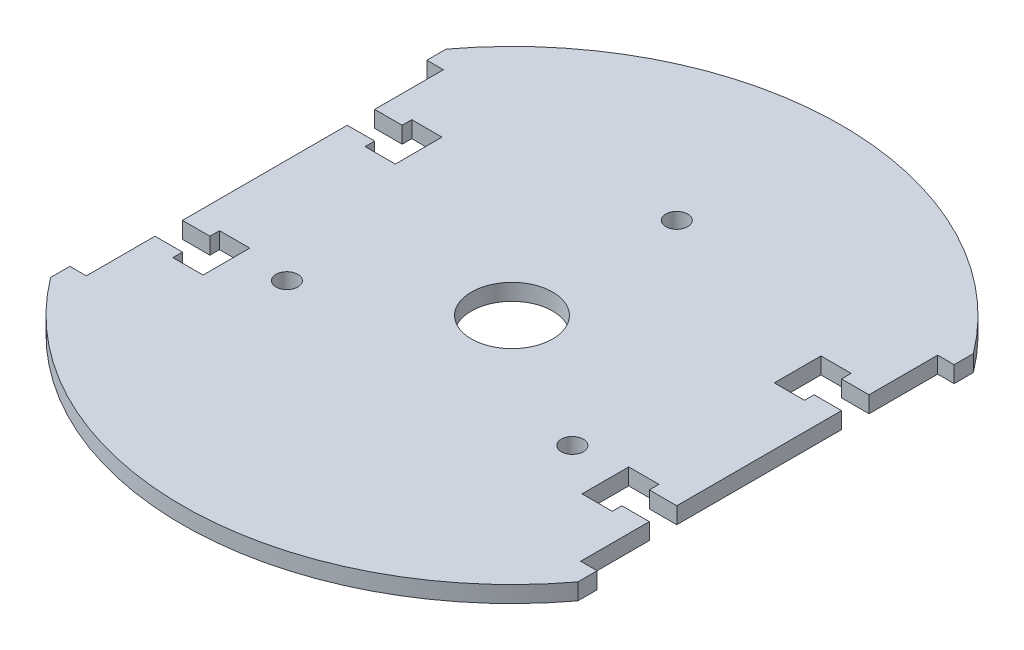
SolidWorks part; units mm, degrees
ref_plane "Front Plane" through (0, 0, 0) normal (0, 0, 1) x (1, 0, 0)
ref_plane "Top Plane" through (0, 0, 0) normal (0, 1, 0) x (1, 0, 0)
ref_plane "Right Plane" through (0, 0, 0) normal (1, 0, 0) x (0, 0, -1)
sketch "Sketch1" plane through (0, 0, 0) normal (0, 1, 0) x (1, 0, 0)
  circle A0 centre (0, 0) radius 60
  dimension "D1" = 120
extrude "Boss-Extrude1" add sketch "Sketch1" along normal blind 3
sketch "Sketch2" plane through (0, 3, 0) normal (0, 1, 0) x (1, 0, 0)
  circle A0 centre (0, 0) radius 7.4
  circle A2 centre (0, 0) radius 31
  dimension "D1" = 62
  dimension "D2" = 14.8
extrude "Cut-Extrude3" cut sketch "Sketch2" against normal through all contours A0
sketch "Sketch3" plane through (0, 3, 0) normal (0, 1, 0) x (1, 0, 0)
  line L0 (-48, 36) -> (-48, -36)
  line L1 (-45, 39.6863) -> (-45, -39.6863)
  line L2 (-48, 32.5) -> (-45, 32.5)
  line L3 (-48, -32.5) -> (-45, -32.5)
  line L4 (-45, 0) -> (-31.0787, 0) construction
  circle A0 centre (0, 0) radius 60 construction
  circle A1 centre (0, 0) radius 60
  circle M1 centre (0, 0) radius 60
  dimension "D1" = 65
  dimension "D2" = 45
  dimension "D3" = 3
  dimension "D4" = 32.5
extrude "Cut-Extrude1" cut sketch "Sketch3" against normal blind 3 contours L0 L3 L1 L2 | L0 M1 region at (-52.8437, 3, 0) region at (-46.5, 3, 0)
sketch "Sketch4" plane through (0, 3, 0) normal (0, 1, 0) x (1, 0, 0)
  line L0 (-45, 32.5) -> (-45, -32.5) construction
  line L1 (-45, 20) -> (-40, 20)
  line L2 (-45, 20) -> (-45, 15)
  line L3 (-45, 15) -> (-40, 15)
  line L4 (-40, 20) -> (-40, 15)
  line L5 (-45, 17.5) -> (-40, 17.5) construction
  line L6 (-40, 21.75) -> (-34.5, 21.75)
  line L7 (-40, 21.75) -> (-40, 13.25)
  line L8 (-40, 13.25) -> (-34.5, 13.25)
  line L9 (-34.5, 21.75) -> (-34.5, 13.25)
  line L10 (-40, 17.5) -> (-34.5, 17.5) construction
  line L11 (-34.5, 17.5) -> (-40, 17.5) construction
  line L12 (-45, 0) -> (0, 0) construction
  line L13 (0, 0) -> (-45, 32.5) construction
  line L14 (-45, 32.5) -> (4.2601, 35.5767) construction
  line L15 (4.2601, 35.5767) -> (-45, 0) construction
  line L16 (-45, 0) -> (-22.5, 16.25) construction
  line L17 (-48, 32.5) -> (-45, 32.5) construction
  line L18 (-22.5, -16.25) -> (-45, -16.25) construction
  line L19 (-45, -16.25) -> (-40, -16.25) construction
  line L20 (-40, -16.25) -> (-45, -16.25) construction
  line L21 (-37, -16.25) -> (-40, -16.25) construction
  line L22 (-34.5, -21.75) -> (-34.5, -13.25)
  line L23 (-40, -13.25) -> (-34.5, -13.25)
  line L24 (-40, -21.75) -> (-40, -13.25)
  line L25 (-40, -21.75) -> (-34.5, -21.75)
  line L26 (-40, -20) -> (-40, -15)
  line L27 (-45, -15) -> (-40, -15)
  line L28 (-45, -20) -> (-45, -15)
  line L29 (-45, -20) -> (-40, -20)
  line L32 (-22.5, 0) -> (-22.5, 16.25) construction
  line L33 (-22.5, 16.25) -> (-33.75, 8.125) construction
  line L34 (-33.75, 8.125) -> (-45, 8.125) construction
  line L35 (-45, 0) -> (-22.5, 16.25) construction
  line L36 (-22.5, 0) -> (-45, 0) construction
  line L37 (-22.5, 0) -> (-45, 0) construction
  line L38 (-45, 0) -> (-40, 0) construction
  line L39 (-40, 0) -> (-45, 0) construction
  line L40 (-37, 0) -> (-40, 0) construction
  line L41 (-34.5, -5.5) -> (-34.5, 3)
  line L42 (-40, 3) -> (-34.5, 3)
  line L43 (-40, -5.5) -> (-40, 3)
  line L44 (-40, -5.5) -> (-34.5, -5.5)
  line L45 (-40, -3.75) -> (-40, 1.25)
  line L46 (-45, 1.25) -> (-40, 1.25)
  line L47 (-45, -3.75) -> (-45, 1.25)
  line L48 (-45, -3.75) -> (-40, -3.75)
  point P13 (-46.5, 32.5)
  line M4 (-45, 32.5) -> (-45, -32.5)
  dimension "D1" = 5
  dimension "D2" = 5.5
  dimension "D3" = 8.5
  dimension "D4" = 5
  dimension "D5" = 15
extrude "Cut-Extrude2" cut sketch "Sketch4" against normal blind 3 contours L9 L6 L7 L4 L8 | L4 L1 L3 M4 | L24 L25 L22 L23 | L29 L24 L27 M4 region at (-42.5, 3, 17.5) region at (-42.5, 3, -17.5) region at (-37.25, 3, -17.5) region at (-37.25, 3, 17.5)
mirror "Mirror1" about plane through (0, 0, 0) normal (1, 0, 0) of "Cut-Extrude2", "Cut-Extrude1"
sketch "Sketch5" plane through (0, 3, 0) normal (0, 1, 0) x (1, 0, 0)
  circle A0 centre (0, 0) radius 31
  dimension "D1" = 62
sketch "Sketch6" plane through (0, 3, 0) normal (0, 1, 0) x (1, 0, 0)
  line L0 (0, 0) -> (0, 60) construction
  line L1 (0, 60) -> (0, -60) construction
  line L2 (-48, 36) -> (48, 36) construction
  arc A0 (48, 36) -> (-48, 36) centre (0, 0) ccw construction
  arc A1 (-48, -36) -> (48, -36) centre (0, 0) ccw construction
  circle A2 centre (25.9808, -15) radius 2
  circle A3 centre (0, 30) radius 2
  circle A5 centre (0, 0) radius 30
  circle A6 centre (-25.9808, -15) radius 2
  point P26 (0, 0)
  dimension "D1" = 3
  dimension "D3" = 60
  dimension "D4" = 4
extrude "Cut-Extrude4" cut sketch "Sketch6" against normal through all contours A5 A6 | A5 A6 | A2 A5 | A5 A2 | A5 A3 | A3 A5 region at (26.7054, 3, 15.4184) region at (25.2354, 3, 14.5696) region at (-26.7054, 3, 15.4184) region at (-25.2354, 3, 14.5696) region at (0, 3, -30.8367) region at (0, 3, -29.1393)
sketch "Sketch7" plane through (0, 3, 0) normal (0, 1, 0) x (1, 0, 0)
  line L1 (-20.7846, 0) -> (-10.3923, -18)
  line L2 (-10.3923, -18) -> (10.3923, -18)
  line L3 (10.3923, -18) -> (20.7846, 0)
  line L4 (20.7846, 0) -> (10.3923, 18)
  line L5 (10.3923, 18) -> (-10.3923, 18)
  line L6 (-10.3923, 18) -> (-20.7846, 0)
  circle A0 centre (0, 0) radius 18 construction
  dimension "D1" = 36
